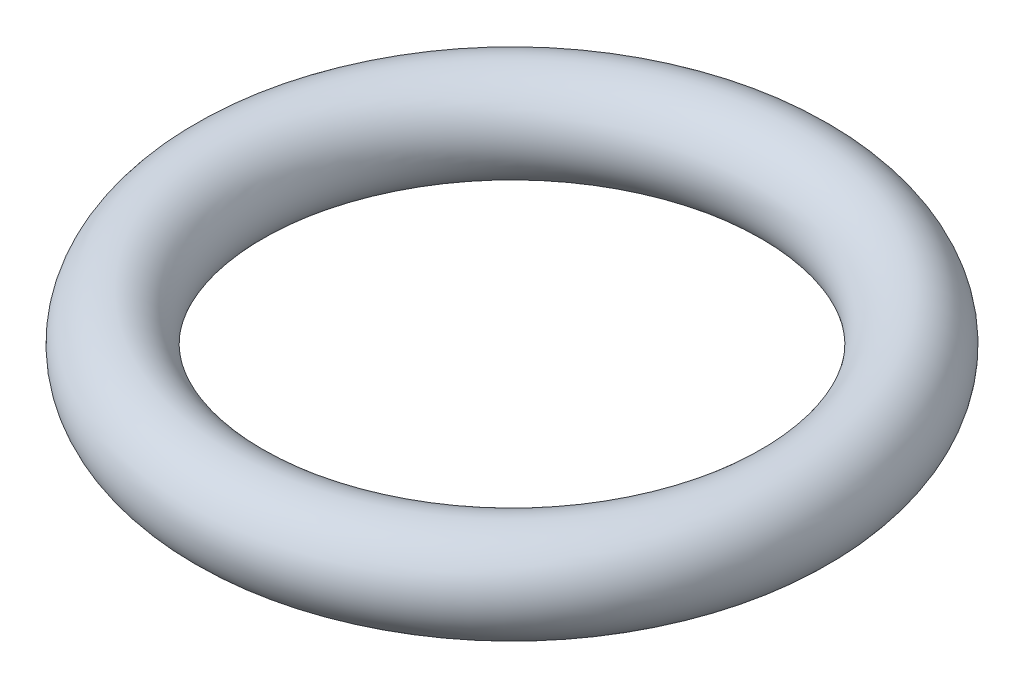
SolidWorks part; units mm, degrees
ref_plane "Front" through (0, 0, 0) normal (0, 0, 1) x (1, 0, 0)
ref_plane "Top" through (0, 0, 0) normal (0, 1, 0) x (1, 0, 0)
ref_plane "Right" through (0, 0, 0) normal (1, 0, 0) x (0, 0, -1)
sketch "Sketch1" plane through (0, 0, 0) normal (1, 0, 0) x (0, 0, -1)
  line L0 (0, -77.3311) -> (0, 77.3311) construction
  line L1 (50, 0) -> (-50, 0) construction
  circle A0 centre (-152.4, 25.4) radius 25.4
  point P4 (0, 0)
  dimension "D1" = 50.8
  dimension "D2" = 254
  dimension "D3" = 355.6
revolve "Revolve1" add sketch "Sketch1" angle 360 about L0
